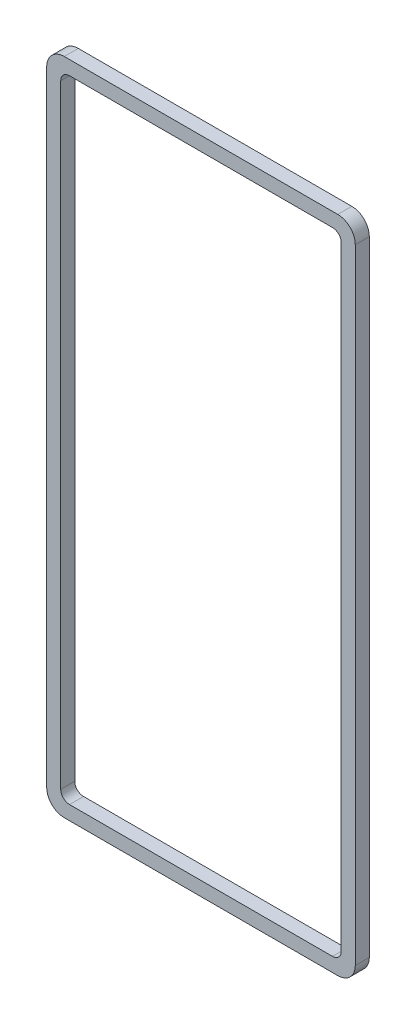
SolidWorks part; units mm, degrees
ref_plane "Plan de face" through (0, 0, 0) normal (0, 0, 1) x (1, 0, 0)
ref_plane "Plan de dessus" through (0, 0, 0) normal (0, 1, 0) x (1, 0, 0)
ref_plane "Plan de droite" through (0, 0, 0) normal (1, 0, 0) x (0, 0, -1)
sketch "Esquisse1" plane through (0, 0, 0) normal (0, 0, 1) x (1, 0, 0)
  line L0 (40, 40) -> (840, 40)
  line L1 (0, 0) -> (880, 0)
  line L2 (0, 0) -> (0, 1880)
  line L3 (0, 1880) -> (880, 1880)
  line L4 (880, 0) -> (880, 1880)
  line L5 (840, 40) -> (840, 1840)
  line L6 (40, 1840) -> (840, 1840)
  line L7 (40, 40) -> (40, 1840)
  dimension "D1" = 880
  dimension "D2" = 1880
  dimension "D3" = 40
extrude "Boss.-Extru.1" add sketch "Esquisse1" along normal blind 40
fillet "Congé1" radius 50 4 edges at (0, 0, 20) (880, 0, 20) (880, 1880, 20) (0, 1880, 20)
fillet "Congé2" radius 25 4 edges at (40, 1840, 20) (40, 40, 20) (840, 40, 20) (840, 1840, 20)
